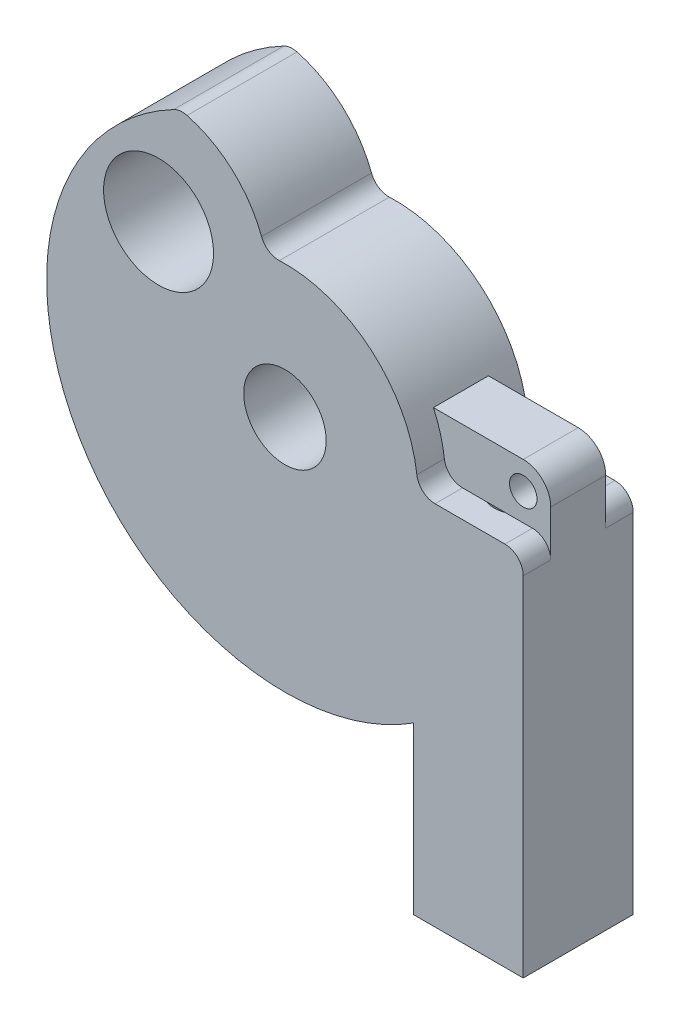
SolidWorks part; units mm, degrees
ref_plane "Front Plane" through (0, 0, 0) normal (0, 0, 1) x (1, 0, 0)
ref_plane "Top Plane" through (0, 0, 0) normal (0, 1, 0) x (1, 0, 0)
ref_plane "Right Plane" through (0, 0, 0) normal (1, 0, 0) x (0, 0, -1)
sketch "Sketch2" plane through (0, 0, 0) normal (0, 0, 1) x (1, 0, 0)
  line L0 (13, 0) -> (13, -20)
  line L1 (13, -20) -> (7, -20)
  line L2 (7, -20) -> (7, -10.9545)
  line L3 (10, 0) -> (10, -20) construction
  arc A0 (13, 0) -> (7, -10.9545) centre (0, 0) ccw
  circle A1 centre (0, 0) radius 10 construction
  dimension "Diameter" = 20
  dimension "Rod Holer Thickness" = 6
  dimension "Rod Holder Length" = 20
extrude "Boss-Extrude1" add sketch "Sketch2" along normal mid plane 6
hole_wizard "M4 Clearance Hole1" positions "Sketch3" profile "Sketch4" hole size "M4" standard "ANSI Metric" end condition up to next
sketch "Sketch3" plane through (0, 0, 3) normal (0, 0, 1) x (1, 0, 0)
  point P2 (0, 0)
sketch "Sketch4" plane through (0, 0, 3) normal (1, 0, 0) x (0, -1, 0)
  line L0 (0, 0) -> (0, 6)
  line L1 (0, 6) -> (2.25, 6)
  line L2 (2.25, 6) -> (2.25, 0)
  line L5 (2.25, 0) -> (0, 0)
  line L11 (0, -6.35) -> (0, 107.95) construction
  dimension "Thru Hole Dia." = 4.5
  dimension "Thru Hole Depth" = 6
sketch "Sketch5" plane through (0, -20, 0) normal (0, -1, 0) x (1, 0, 0)
  line L0 (13, 3) -> (7, -3) construction
  circle A0 centre (10, 0) radius 1.59
  dimension "Rod Hole Diameter" = 3.18
extrude "Cut-Extrude1" cut sketch "Sketch5" against normal blind 20
ref_axis "Axis1" through (10, 0, 0) along (0, -1, 0)
sketch "Sketch8" plane through (0, 0, 3) normal (0, 0, 1) x (1, 0, 0)
  line L0 (0, 0) -> (-21.8723, 0) construction
  line L1 (0, 0) -> (-6.8944, 5.7851) construction
  circle A0 centre (-6.8944, 5.7851) radius 3
  dimension "D2" = 6
  dimension "D1" = 40
  dimension "D3" = 9
extrude "Cut-Extrude3" cut sketch "Sketch8" against normal through all
sketch "Sketch9" plane through (0, 0, 3) normal (0, 0, 1) x (1, 0, 0)
  line L1 (13, 0) -> (7.25, 0)
  line L2 (13, 0) -> (13, 10.075) construction
  arc A0 (13, 0) -> (7, -10.9545) centre (0, 0) ccw construction
  arc A1 (7.25, 0) -> (-1.057, 7.1725) centre (0, 0) ccw
  circle A2 centre (0, 0) radius 2.25 construction
  arc A4 (-1.057, 7.1725) -> (-5.7272, 11.6705) centre (-6.8944, 5.7851) ccw
  circle A5 centre (-6.8944, 5.7851) radius 3 construction
  arc A6 (13, 0) -> (-5.7272, 11.6705) centre (0, 0) ccw
  dimension "D1" = 5
  dimension "D2" = 3
extrude "Cut-Extrude4" cut sketch "Sketch9" against normal through all
sketch "Sketch6" plane through (0, 0, 0) normal (0, 0, 1) x (1, 0, 0)
  line L4 (13, 1.5) -> (13, 0)
  line L6 (11.5, 3) -> (6.6002, 3)
  line L8 (7.25, 0) -> (13, 0) construction
  line L9 (7.25, 0) -> (13, 0)
  arc A2 (13, 1.5) -> (11.5, 3) centre (11.5, 1.5) ccw
  arc A3 (7.25, 0) -> (-1.057, 7.1725) centre (0, 0) ccw construction
  arc A4 (7.25, 0) -> (6.6002, 3) centre (0, 0) ccw
  point P0 (13.2864, 0.2615)
  dimension "Spring Attchment Diameter" = 1.5
extrude "Boss-Extrude2" add sketch "Sketch6" along normal mid plane 3
fillet "Fillet1" radius 1 6 edges at (-5.7272, 11.6705, 0) (7.25, 0, 2.25) (7.25, 0, -2.25) (-1.057, 7.1725, 0) (13, 0, -2.25) (13, 0, 2.25)
sketch "Sketch7" plane through (0, 0, 1.5) normal (0, 0, 1) x (1, 0, 0)
  circle A0 centre (11.5, 1.5) radius 0.75
  arc A1 (13, 1.5) -> (11.5, 3) centre (11.5, 1.5) ccw construction
  dimension "Spring Hole Diam" = 1.5
extrude "Cut-Extrude2" cut sketch "Sketch7" against normal through all both and the other way through all
